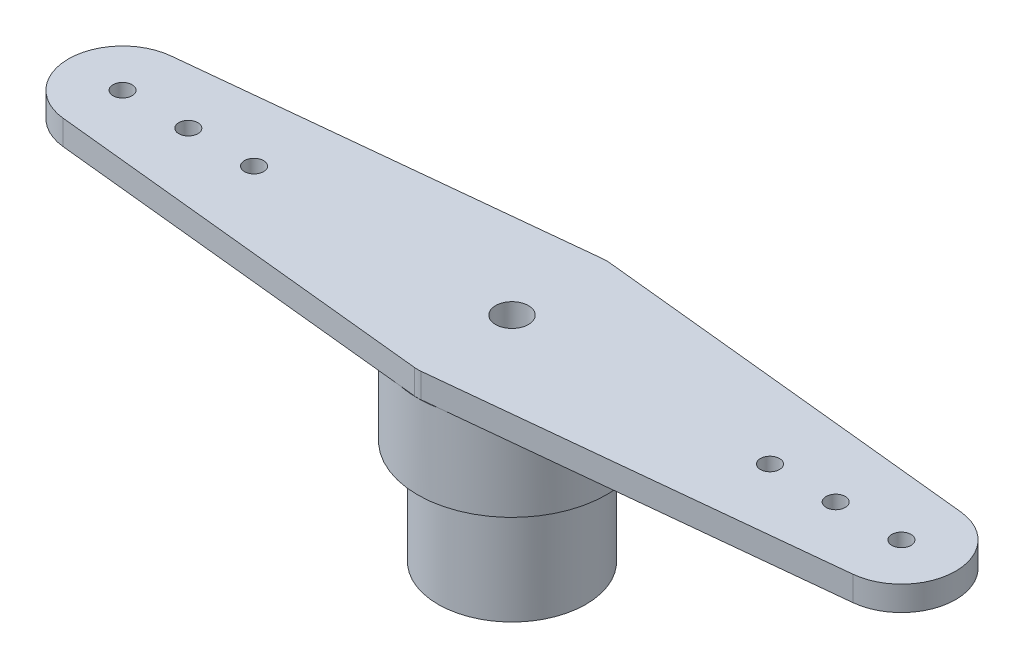
SolidWorks part; units mm, degrees
ref_plane "Front" through (0, 0, 0) normal (0, 0, 1) x (1, 0, 0)
ref_plane "Top" through (0, 0, 0) normal (0, 1, 0) x (1, 0, 0)
ref_plane "Right" through (0, 0, 0) normal (1, 0, 0) x (0, 0, -1)
sketch "Sketch1" plane through (0, 0, 0) normal (0, 1, 0) x (1, 0, 0)
  line L0 (0, 0) -> (-13.5, 0) construction
  line L1 (0, 0) -> (0, 2.875) construction
  line L2 (-12.0185, 1.6414) -> (0, 2.875)
  line L3 (-13.5, 0) -> (-13.5, 2.7686) construction
  line L4 (-12.0185, -1.6414) -> (0, -2.875)
  line L5 (12.0185, -1.6414) -> (0, -2.875)
  line L6 (12.0185, 1.6414) -> (0, 2.875)
  line L7 (13.5, 0) -> (13.5, 1.0183) construction
  circle A0 centre (0, 0) radius 2.875
  arc A1 (-12.0185, 1.6414) -> (-12.0185, -1.6414) centre (-11.85, 0) ccw
  arc A2 (12.0185, 1.6414) -> (12.0185, -1.6414) centre (11.85, 0) cw
  circle A3 centre (-11.85, 0) radius 0.2914
  circle A4 centre (-9.85, 0) radius 0.2914
  circle A5 centre (-7.85, 0) radius 0.2914
  circle A6 centre (7.85, 0) radius 0.2914
  circle A7 centre (9.85, 0) radius 0.2914
  circle A8 centre (11.85, 0) radius 0.2914
  dimension "D1" = 5.75
  dimension "D4" = 1.65
  dimension "D2" = 3
  dimension "D3" = 27
extrude "Boss-Extrude1" add sketch "Sketch1" against normal blind 2.55 contours A0
extrude "Boss-Extrude2" add sketch "Sketch1<4>" along normal blind 0.75 contours L2 A1 L4 A0 A5 A4 A3 | A2 L6 A0 L5 A7 A6 A8 | L5 A0 L6 L2 L4 region at (-7.2307, 0, 0) region at (0, 0, 0) region at (7.2307, 0, 0)
sketch "Sketch1<4>" plane through (0, 0, 0) normal (0, 1, 0) x (1, 0, 0) same geometry as "Sketch1"
sketch "Sketch2" plane through (0, -2.55, 0) normal (0, -1, 0) x (1, 0, 0)
  circle A0 centre (0, 0) radius 2.25
  dimension "D1" = 4.5
extrude "Boss-Extrude3" add sketch "Sketch2" along normal blind 3.2
sketch "Sketch3" plane through (0, -5.75, 0) normal (0, -1, 0) x (1, 0, 0)
  circle A0 centre (0, 0) radius 0.5
  dimension "D1" = 1
extrude "Cut-Extrude1" cut sketch "Sketch3" against normal through all
fillet "Fillet1" radius 1 2 edges at (0, 0.375, 2.875) (0, 0.375, -2.875)
